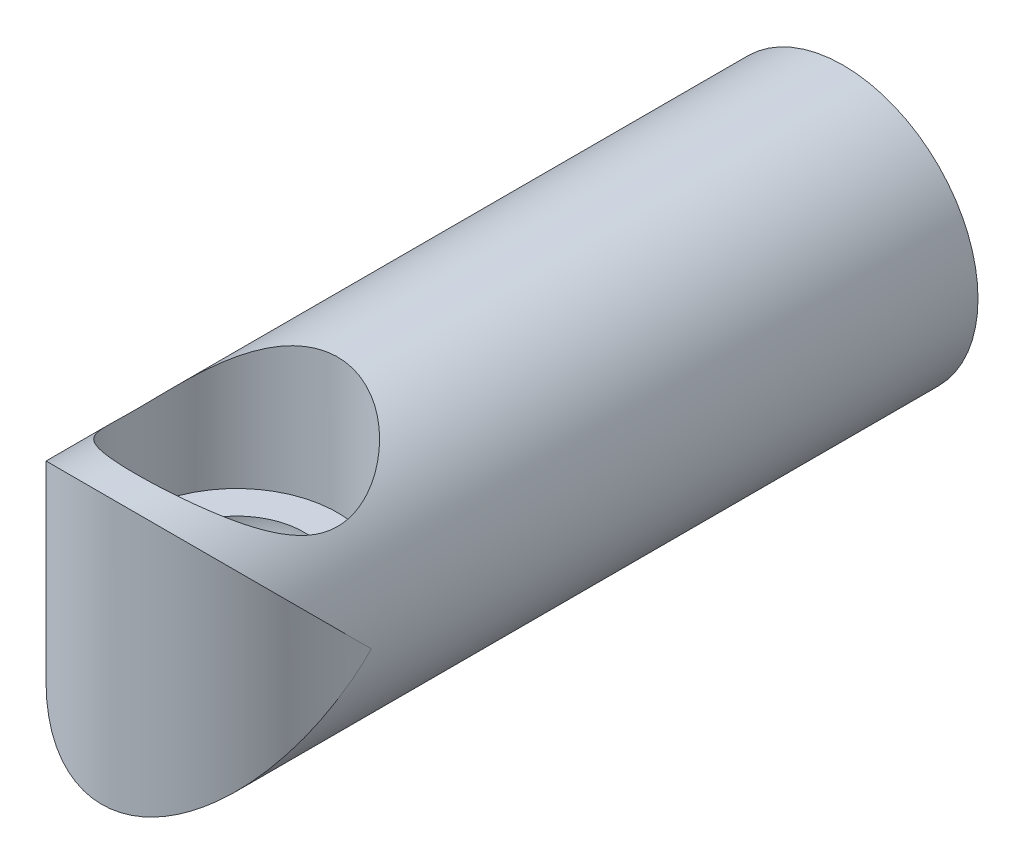
SolidWorks part; units mm, degrees
ref_plane "Plan de face" through (0, 0, 0) normal (0, 0, 1) x (1, 0, 0)
ref_plane "Plan de dessus" through (0, 0, 0) normal (0, 1, 0) x (1, 0, 0)
ref_plane "Plan de droite" through (0, 0, 0) normal (1, 0, 0) x (0, 0, -1)
sketch "Esquisse1" plane through (0, 0, 0) normal (0, 0, 1) x (1, 0, 0)
  circle A0 centre (0, 0) radius 2
  circle A1 centre (0, 0) radius 1
  circle A2 centre (0, 0) radius 1
  dimension "D2" = 1
  dimension "D1" = 0
extrude "Boss.-Extru.1" add sketch "Esquisse1" against normal blind 5 and the other way blind 2 contours A0 | A2
sketch "Esquisse2" plane through (0, 0, 0) normal (0, 1, 0) x (1, 0, 0)
  line L0 (-2, -2) -> (-2, -4)
  line L1 (2, -2) -> (2, -4)
  line L2 (-2, -2) -> (2, -2) construction
  line L3 (-2, -2) -> (2, -2)
  circle A0 centre (0, -4) radius 1 construction
  arc A1 (-2, -4) -> (2, -4) centre (0, -4) ccw
  point P7 (0, -4.3841)
  dimension "D1" = 2
  dimension "D2" = 2
extrude "Boss.-Extru.2" add sketch "Esquisse2" along normal up to surface and the other way up to surface up to face at (2, 0, 2) other way up to face at (2, 0, 2)
sketch "Esquisse3" plane through (0, 0, 0) normal (1, 0, 0) x (0, 0, -1)
  line L0 (-4, -1) -> (-4, 1)
  arc A0 (-4, 1) -> (-4, -1) centre (-4, 0) cw
  point P4 (0, 0)
  dimension "D1" = 1
revolve "Enlèvement de matière-Révolution1" cut sketch "Esquisse3" angle 360 about L0
ref_plane "Plan1" through (0, 2, 0) normal (0, 1, 0) x (1, 0, 0)
sketch "Esquisse4" plane through (0, 2, 0) normal (0, 1, 0) x (1, 0, 0)
  circle A0 centre (0, -4) radius 1.5
  circle A1 centre (0, -4) radius 1 construction
  arc A4 (-2, -4) -> (2, -4) centre (0, -4) ccw construction
  dimension "D1" = 0.5
extrude "Enlèv. mat.-Extru.1" cut sketch "Esquisse4" against normal up to surface (2 mm away) up to plane "Plan de dessus"
